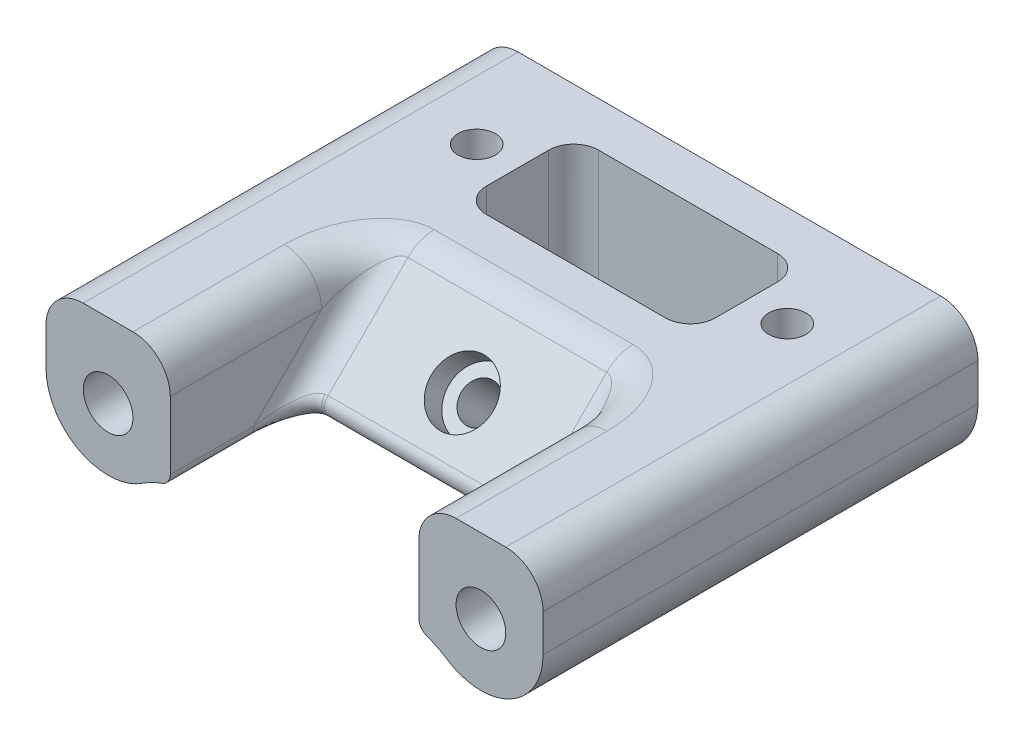
SolidWorks part; units mm, degrees
ref_plane "Front Plane" through (0, 0, 0) normal (0, 0, 1) x (1, 0, 0)
ref_plane "Top Plane" through (0, 0, 0) normal (0, 1, 0) x (1, 0, 0)
ref_plane "Right Plane" through (0, 0, 0) normal (1, 0, 0) x (0, 0, -1)
sketch "Sketch2" plane through (0, 0, 0) normal (0, 0, 1) x (1, 0, 0)
  line L0 (20, 37) -> (20, 40)
  line L2 (17, 43) -> (-17, 43)
  line L3 (-20, 40) -> (-20, 37)
  line L5 (8.3668, 34) -> (-8.3668, 34)
  circle A1 centre (15, 37) radius 2
  circle A3 centre (-15, 37) radius 2
  arc A4 (-20, 37) -> (-12.2361, 32.8333) centre (-15, 37) ccw
  arc A5 (12.2361, 32.8333) -> (20, 37) centre (15, 37) ccw
  arc A6 (20, 40) -> (17, 43) centre (17, 40) ccw
  arc A7 (-17, 43) -> (-20, 40) centre (-17, 40) ccw
  arc A8 (-8.3668, 34) -> (-12.2361, 32.8333) centre (-8.3668, 27) ccw
  arc A9 (8.3668, 34) -> (12.2361, 32.8333) centre (8.3668, 27) cw
  dimension "D1" = 7
  dimension "D2" = 9
extrude "Boss-Extrude1" add sketch "Sketch2" along normal up to surface (35 mm away)
sketch "Sketch4" plane through (0, 0, 0) normal (1, 0, 0) x (0, 0, -1)
  line L1 (-35, 43) -> (-17, 43)
  line L2 (-35, 43) -> (-35, 32)
  line L3 (-35, 32) -> (-28, 32)
  line L5 (-17, 43) -> (-28, 32)
extrude "Cut-Extrude2" cut sketch "Sketch4" against normal mid plane 20
sketch "Sketch5" plane through (0, 43, 0) normal (0, 1, 0) x (1, 0, 0)
  line L0 (8.2585, -9.6015) -> (8.2585, -6.6015) construction
  line L1 (7.4585, -12.6015) -> (-6.9415, -12.6015)
  line L2 (9.4585, -10.6015) -> (9.4585, -5.6015)
  line L3 (7.4585, -3.6015) -> (-6.9415, -3.6015)
  line L4 (-8.9415, -10.6015) -> (-8.9415, -5.6015)
  line L5 (-7.7415, -6.6015) -> (-7.7415, -9.6015) construction
  line L6 (-5.7415, -11.6015) -> (6.2585, -11.6015) construction
  line L7 (6.2585, -4.6015) -> (-5.7415, -4.6015) construction
  arc A0 (-6.9415, -12.6015) -> (-8.9415, -10.6015) centre (-6.9415, -10.6015) cw
  arc A1 (-6.9415, -3.6015) -> (-8.9415, -5.6015) centre (-6.9415, -5.6015) ccw
  arc A2 (9.4585, -5.6015) -> (7.4585, -3.6015) centre (7.4585, -5.6015) ccw
  arc A3 (7.4585, -12.6015) -> (9.4585, -10.6015) centre (7.4585, -10.6015) ccw
  dimension "D5" = 2
  dimension "D1" = 1.2
  dimension "D2" = 1.2
  dimension "D3" = 1
  dimension "D4" = 1
extrude "Cut-Extrude3" cut sketch "Sketch5" against normal through all
fillet "Fillet1" radius 2 2 edges at (-10, 38.4034, 21.5966) (10, 38.4034, 21.5966)
sketch "Sketch6" plane through (0, 43, 0) normal (0, 1, 0) x (1, 0, 0)
  circle A0 centre (12.7585, -8.1015) radius 1.5
  circle A1 centre (-12.2415, -8.1015) radius 1.5
extrude "Cut-Extrude4" cut sketch "Sketch6" against normal blind 5
sketch "Sketch7" plane through (0, 30, 30) normal (0, 0.7071, 0.7071) x (1, 0, 0)
  line L0 (0, 5.6569) -> (0, 18.3848) construction
  line L1 (8, 5.6569) -> (-8, 5.6569) construction
  line L2 (-8, 18.3848) -> (8, 18.3848) construction
  circle A0 centre (0, 12.0208) radius 2.5
extrude "Cut-Extrude5" cut sketch "Sketch7" against normal blind 2
sketch "Sketch8" plane through (0, 28.5858, 28.5858) normal (0, 0.7071, 0.7071) x (1, 0, 0)
  circle A0 centre (0, 12.0208) radius 1.5
extrude "Cut-Extrude6" cut sketch "Sketch8" against normal through all
fillet "Fillet2" radius 3 5 edges at (-10, 43, 27.4142) (-9.4142, 43, 17.8284) (10, 43, 27.4142) (9.4142, 43, 17.8284) (0, 43, 17)
fillet "Fillet3" radius 1 7 edges at (10, 33.8068, 32.0108) (9.3051, 33.9368, 26.7484) (8.1842, 34, 26.012) (-10, 33.8068, 32.0108) (-9.3627, 33.9288, 26.8293) (-8.1842, 34, 26.012) (0, 34, 26)
